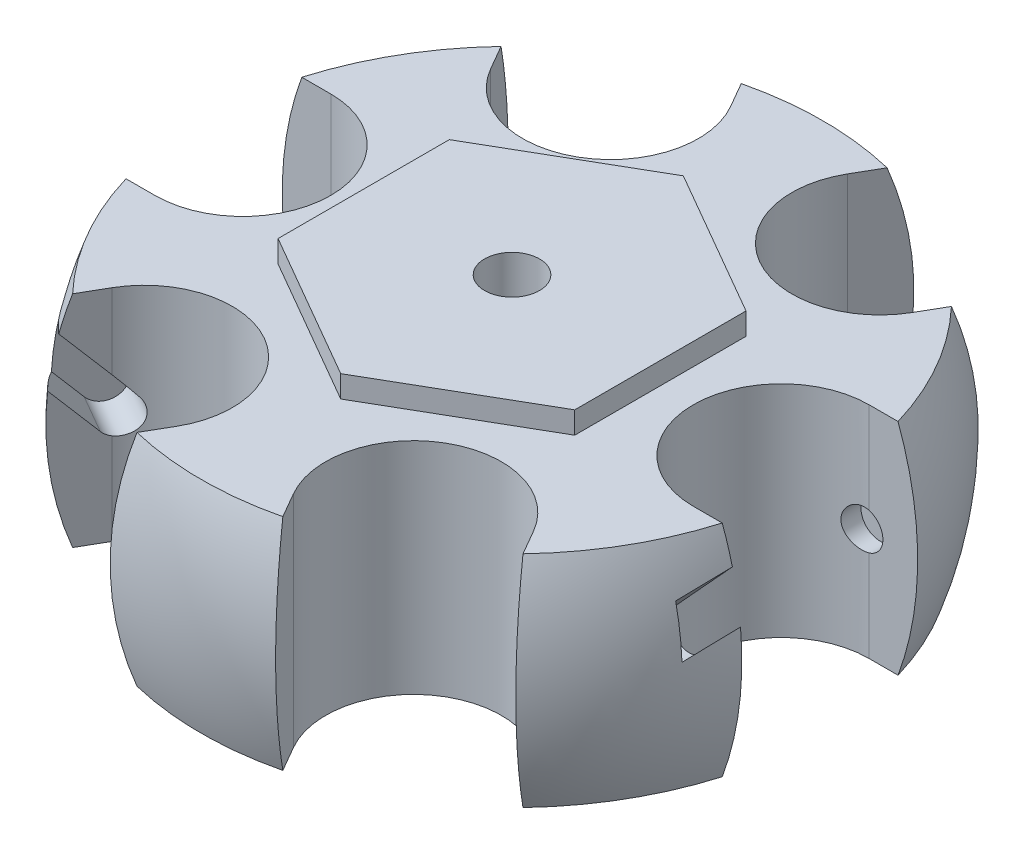
SolidWorks part; units mm, degrees
ref_plane "Front Plane" through (0, 0, 0) normal (0, 0, 1) x (1, 0, 0)
ref_plane "Top Plane" through (0, 0, 0) normal (0, 1, 0) x (1, 0, 0)
ref_plane "Right Plane" through (0, 0, 0) normal (1, 0, 0) x (0, 0, -1)
sketch "Sketch1" plane through (0, 0, 0) normal (0, 0, 1) x (1, 0, 0)
  line L0 (0, 0) -> (0, 147.1733) construction
  line L1 (0, 0) -> (0, 60)
  line L2 (0, 0) -> (0, -60)
  arc A0 (0, -60) -> (0, 60) centre (0, 0) cw
  dimension "D1" = 60
revolve "Revolve1" add sketch "Sketch1" angle 360 about L0
ref_plane "Plane4" through (0, 20, 0) normal (0, 1, 0) x (1, 0, 0)
ref_plane "Plane5" through (0, -20, 0) normal (0, 1, 0) x (1, 0, 0)
sketch "Sketch2" plane through (0, 20, 0) normal (0, 1, 0) x (1, 0, 0)
  line L1 (-66.1971, 65.6494) -> (70.7355, 65.6494)
  line L2 (-66.1971, 65.6494) -> (-66.1971, -69.0923)
  line L3 (-66.1971, -69.0923) -> (70.7355, -69.0923)
  line L4 (70.7355, 65.6494) -> (70.7355, -69.0923)
extrude "Cut-Extrude1" cut sketch "Sketch2" along normal through all
sketch "Sketch3" plane through (0, -20, 0) normal (0, 1, 0) x (1, 0, 0)
  line L5 (-74.8043, 65.6494) -> (82.629, 65.6494)
  line L6 (-74.8043, 65.6494) -> (-74.8043, -70.6572)
  line L7 (-74.8043, -70.6572) -> (82.629, -70.6572)
  line L8 (82.629, 65.6494) -> (82.629, -70.6572)
extrude "Cut-Extrude2" cut sketch "Sketch3" against normal through all
ref_axis "Axis1" through (0, 0, 0) along (0, 1, 0)
ref_plane "Plane6" through (0, 0, 0) normal (0.5, 0, -0.866) x (0, 1, 0)
ref_plane "Plane7" through (0, 0, 0) normal (-0.5, 0, -0.866) x (0, 1, 0)
sketch "Sketch5" plane through (0, 0, 0) normal (-0.5, 0, -0.866) x (0, 1, 0)
  line L0 (20, -66) -> (20, 66) construction
  arc A0 (20, -56.5685) -> (20, 56.5685) centre (0, 0) ccw
  arc A1 (-20, -56.5685) -> (20, -56.5685) centre (0, 0) ccw construction
  arc A2 (20, 56.5685) -> (-20, 56.5685) centre (0, 0) ccw construction
sketch "Sketch6" plane through (0, 0, 0) normal (0.5, 0, -0.866) x (0, 1, 0)
  line L0 (20, -66) -> (20, 66) construction
  arc A0 (20, -56.5685) -> (20, 56.5685) centre (0, 0) ccw
  arc A1 (-20, -56.5685) -> (20, -56.5685) centre (0, 0) ccw construction
  arc A2 (20, 56.5685) -> (-20, 56.5685) centre (0, 0) ccw construction
sketch "Sketch7" plane through (0, 20, 0) normal (0, 1, 0) x (1, 0, 0)
  line L0 (48.9898, 28.2843) -> (48.9898, -28.2843) construction
  line L1 (48.9898, 28.2843) -> (-48.9898, -28.2843) construction
  line L2 (25.1494, 14.52) -> (-25.1494, -14.52) construction
  line L3 (48.9898, -28.2843) -> (-48.9898, 28.2843) construction
  line L4 (48.9898, 16) -> (63.0307, 16)
  line L5 (63.0307, 16) -> (63.0307, -16)
  line L6 (63.0307, -16) -> (48.9898, -16)
  circle A0 centre (0, 0) radius 56.5685 construction
  arc A1 (48.9898, 16) -> (48.9898, -16) centre (48.9898, 0) ccw
  dimension "D1" = 16
extrude "Cut-Extrude3" cut sketch "Sketch7" against normal through all
sketch "Sketch8" plane through (0, 0, -16) normal (0, 0, 1) x (1, 0, 0)
  line L0 (64.805, 20) -> (-64.805, 20) construction
  line L1 (0, 0) -> (0, 52.8) construction
  circle A0 centre (48, 0) radius 3.5
  dimension "D1" = 7
  dimension "D2" = 20
  dimension "D3" = 48
extrude "Cut-Extrude4" cut sketch "Sketch8" against normal blind 3 and the other way blind 40
ref_plane "Plane8" through (0, 0, 0) normal (0, 0, 1) x (1, 0, 0)
sketch "Sketch9" plane through (0, 0, 0) normal (0, 0, 1) x (1, 0, 0)
  line L0 (45.4223, 2.3676) -> (57.9462, 16.0025)
  line L1 (50.5777, -2.3676) -> (63.1015, 11.2672)
  line L2 (63.1015, 11.2672) -> (57.9462, 16.0025)
  arc A0 (45.4223, 2.3676) -> (50.5777, -2.3676) centre (48, 0) ccw
  point P7 (7.8686, 3.2268)
  point P9 (0, 0)
  dimension "D1" = 7
extrude "Cut-Extrude5" cut sketch "Sketch9" along normal up to surface (24 mm away) up to face at (51.5, 0, 24)
pattern_circular "CirPattern1" count 6 over 360 about axis through (0, 0, 0) along (0, 1, 0) of "Cut-Extrude3"
pattern_circular "CirPattern2" count 3 every 120 about axis through (0, 0, 0) along (0, 1, 0) of "Cut-Extrude4", "Cut-Extrude5"
sketch "Sketch10" plane through (0, 20, 0) normal (0, 1, 0) x (1, 0, 0)
  line L1 (27, -15.5885) -> (27, 15.5885)
  line L2 (27, 15.5885) -> (0, 31.1769)
  line L3 (0, 31.1769) -> (-27, 15.5885)
  line L4 (-27, 15.5885) -> (-27, -15.5885)
  line L5 (-27, -15.5885) -> (0, -31.1769)
  line L6 (0, -31.1769) -> (27, -15.5885)
  circle A0 centre (0, 0) radius 27 construction
  dimension "D1" = 54
extrude "Boss-Extrude1" add sketch "Sketch10" along normal blind 4
sketch "Sketch11" plane through (0, -20, 0) normal (0, -1, 0) x (1, 0, 0)
  line L1 (27, -15.5885) -> (27, 15.5885)
  line L2 (27, 15.5885) -> (0, 31.1769)
  line L3 (0, 31.1769) -> (-27, 15.5885)
  line L4 (-27, 15.5885) -> (-27, -15.5885)
  line L5 (-27, -15.5885) -> (0, -31.1769)
  line L6 (0, -31.1769) -> (27, -15.5885)
  circle A0 centre (0, 0) radius 27 construction
  dimension "D1" = 54
extrude "Cut-Extrude6" cut sketch "Sketch11" against normal blind 5
sketch "Sketch12" plane through (0, 24, 0) normal (0, 1, 0) x (1, 0, 0)
  circle A0 centre (0, 0) radius 5
  dimension "D1" = 10
extrude "Cut-Extrude7" cut sketch "Sketch12" against normal through all
